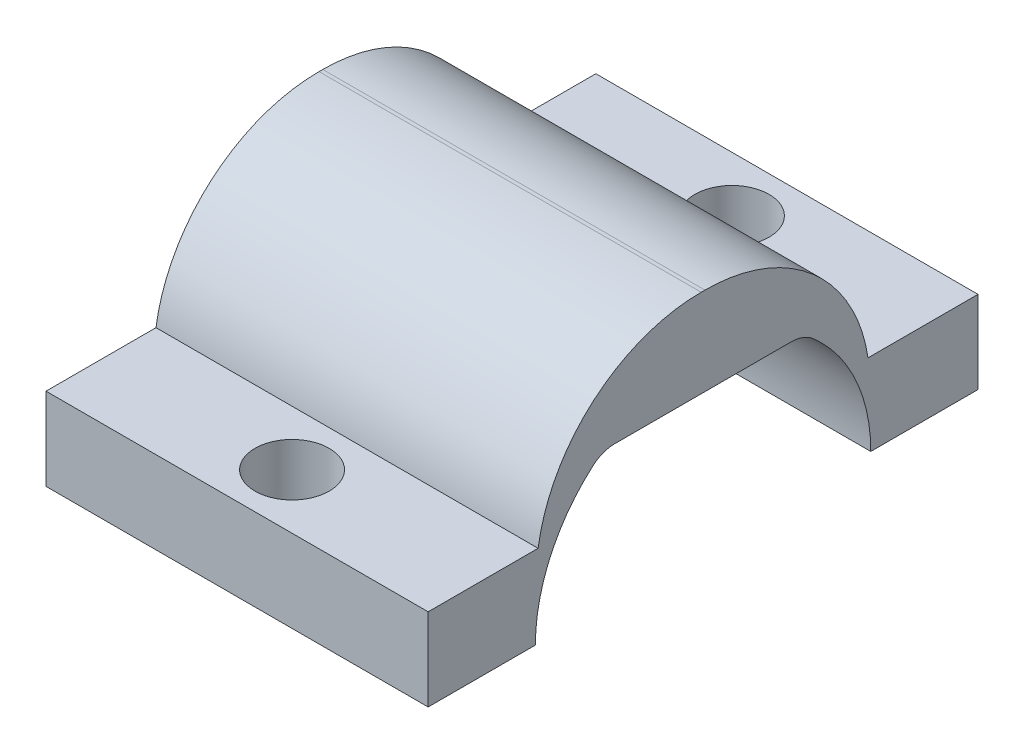
SolidWorks part; units mm, degrees
ref_plane "Plano frontal" through (0, 0, 0) normal (0, 0, 1) x (1, 0, 0)
ref_plane "Plano superior" through (0, 0, 0) normal (0, 1, 0) x (1, 0, 0)
ref_plane "Plano direito" through (0, 0, 0) normal (1, 0, 0) x (0, 0, -1)
sketch "Esboço1" plane through (0, 0, 0) normal (1, 0, 0) x (0, 0, -1)
  line L0 (0, -6.1) -> (0, -5.1)
  line L1 (0, 6.1) -> (0, 4.9)
  line L2 (-6.1, 0) -> (6.1, 0)
  line L3 (-3.6332, 4.9) -> (3.6332, 4.9)
  line L4 (-6.1, 0) -> (-10, 0)
  line L5 (6.1, 0) -> (10, 0)
  line L6 (-10, 0) -> (-10, 3)
  line L7 (10, 0) -> (10, 3)
  line L8 (-10, 3) -> (-6, 3)
  line L9 (-6, 3) -> (-6, 8.1)
  line L10 (-6, 8.1) -> (6, 8.1)
  line L11 (10, 3) -> (6, 3)
  line L12 (6, 3) -> (6, 8.1)
  circle A0 centre (0, 0) radius 6.1
  point P12 (0, 4.9)
  dimension "D1" = 12.2
  dimension "D2" = 1.2
  dimension "D3" = 1
  dimension "D4" = 3.9
  dimension "D5" = 3.9
  dimension "D6" = 3
  dimension "D7" = 3
  dimension "D8" = 2
extrude "Ressalto-extrusão1" add sketch "Esboço1" along normal blind 13.9 contours A0 L5 L7 L11 L12 L10 L9 L8 L6 L4 | L1 A0 L3 | L3 A0 L1 region at (0, 5.3843, -1.3823) region at (0, 5.9971, 1.9808) region at (0, 5.3843, 1.3823)
fillet "Filete1" radius 6 2 edges at (6.95, 8.1, 6) (6.95, 8.1, -6)
sketch "Esboço2" plane through (0, 3, 0) normal (0, 1, 0) x (1, 0, 0)
  line L0 (6.95, -6) -> (6.95, -10)
  line L1 (13.9, -6) -> (0, -6) construction
  line L2 (13.9, -10) -> (0, -10) construction
  line L3 (6.95, 6) -> (6.95, 10)
  line L4 (13.9, 6) -> (0, 6) construction
  line L5 (13.9, 10) -> (0, 10) construction
  circle A0 centre (6.95, 8) radius 1.35
  circle A1 centre (6.95, -8) radius 1.35
  dimension "D1" = 2.7
  dimension "D2" = 2.7
extrude "Corte-extrusão1" cut sketch "Esboço2" against normal blind 13.9 contours L3 A0 | L3 A0 | L0 A1 | L0 A1 region at (7.523, 3, 8) region at (6.377, 3, 8) region at (6.377, 3, -8) region at (7.523, 3, -8)
fillet "Filete2" radius 1.2 2 edges at (6.95, 4.9, -3.6332) (6.95, 4.9, 3.6332)
